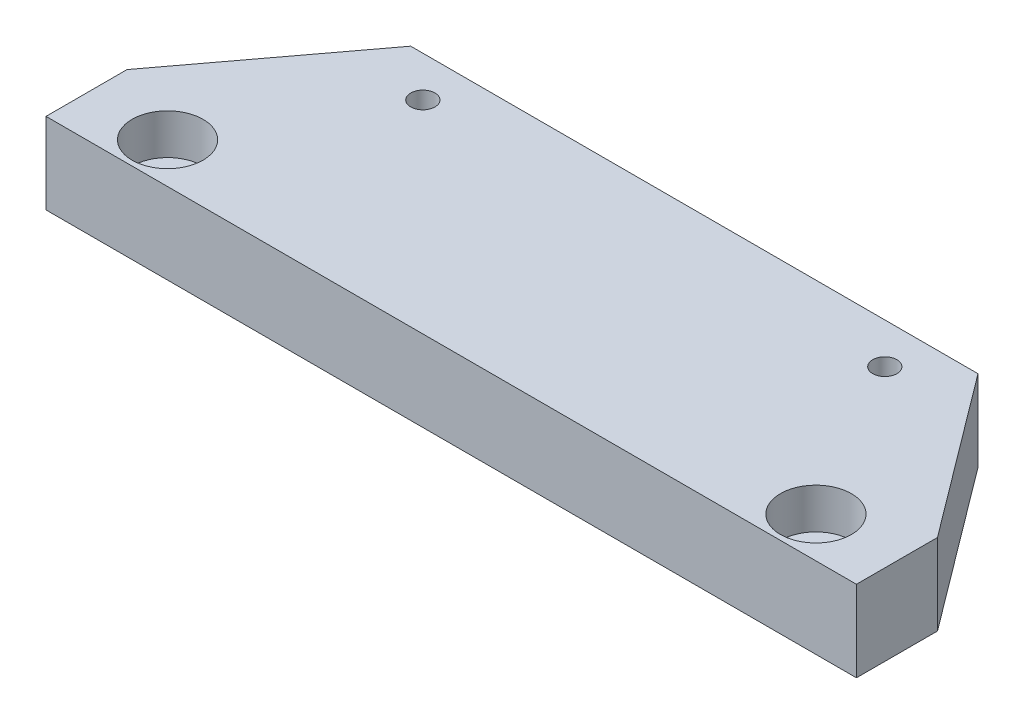
SolidWorks part; units mm, degrees
ref_plane "Front Plane" through (0, 0, 0) normal (0, 0, 1) x (1, 0, 0)
ref_plane "Top Plane" through (0, 0, 0) normal (0, 1, 0) x (1, 0, 0)
ref_plane "Right Plane" through (0, 0, 0) normal (1, 0, 0) x (0, 0, -1)
sketch "Sketch8" plane through (0, 0, 0) normal (0, 1, 0) x (1, 0, 0)
  line L0 (44.45, 0) -> (44.45, -12.7)
  line L1 (0, 0) -> (88.9, 0)
  line L2 (0, 0) -> (0, -12.7)
  line L3 (0, -12.7) -> (88.9, -12.7)
  line L4 (88.9, 0) -> (88.9, -12.7)
  line L5 (8.255, -6.35) -> (80.645, -6.35)
  line L6 (44.45, -12.7) -> (44.45, -31.75)
  line L7 (0, 0) -> (-19.05, -25.4)
  line L8 (-19.05, -25.4) -> (107.95, -25.4)
  line L9 (-19.05, -25.4) -> (-19.05, -38.1)
  line L10 (-19.05, -38.1) -> (107.95, -38.1)
  line L11 (107.95, -25.4) -> (107.95, -38.1)
  line L12 (-19.05, -25.4) -> (107.95, -38.1) construction
  line L13 (-19.05, -38.1) -> (107.95, -25.4) construction
  line L14 (88.9, 0) -> (107.95, -25.4)
  line L15 (95.25, -31.75) -> (-6.35, -31.75)
  point P10 (44.45, -6.35)
  point P23 (44.45, -31.75)
  dimension "D1" = 12.7
  dimension "D2" = 88.9
  dimension "D3" = 72.39
  dimension "D4" = 12.7
  dimension "D5" = 127
  dimension "D6" = 12.7
  dimension "D7" = 101.6
extrude "Boss-Extrude3" add sketch "Sketch8" along normal blind 12.7 contours L7 L8 L6 L3 L2 | L14 L4 L3 L6 L8 | L9 L8 L11 L10 | L2 L1 L4 L3 region at (13.6525, 0, 18.415) region at (75.2475, 0, 18.415)
hole_wizard "CBORE for #6 Socket Head Cap Screw1" positions "Sketch11" profile "Sketch12" counterbore size "#6" standard "ANSI Inch" end condition up to next
sketch "Sketch11" plane through (0, 0, 0) normal (0, -1, 0) x (-1, 0, 0)
  point P0 (-80.645, -6.35)
  point P3 (-8.255, -6.35)
sketch "Sketch12" plane through (80.645, 0, 6.35) normal (1, 0, 0) x (0, 0, -1)
  line L0 (0, 0) -> (0, 12.7)
  line L1 (0, 12.7) -> (1.8986, 12.7)
  line L3 (1.8986, 12.7) -> (1.8986, 3.5052)
  line L4 (1.8986, 3.5052) -> (3.5725, 3.5052)
  line L5 (3.5725, 3.5052) -> (3.5725, 0)
  line L7 (3.5725, 0) -> (0, 0)
  line L11 (0, -6.35) -> (0, 107.95) construction
  dimension "Thru Hole Dia." = 3.7973
  dimension "Thru Hole Depth" = 12.7
  dimension "C'Bore Dia." = 7.145
  dimension "C'Bore Depth" = 3.5052
hole_wizard "CBORE for 1/4 Socket Head Cap Screw1" positions "Sketch13" profile "Sketch14" counterbore size "1/4" standard "ANSI Inch" end condition up to next
sketch "Sketch13" plane through (0, 12.7, 0) normal (0, 1, 0) x (1, 0, 0)
  point P0 (-6.35, -31.75)
  point P3 (95.25, -31.75)
sketch "Sketch14" plane through (-6.35, 12.7, 31.75) normal (1, 0, 0) x (0, 0, 1)
  line L0 (0, 0) -> (0, 12.7)
  line L1 (0, 12.7) -> (3.3782, 12.7)
  line L3 (3.3782, 12.7) -> (3.3782, 6.35)
  line L4 (3.3782, 6.35) -> (5.5562, 6.35)
  line L5 (5.5562, 6.35) -> (5.5562, 0)
  line L7 (5.5562, 0) -> (0, 0)
  line L11 (0, -6.35) -> (0, 107.95) construction
  dimension "Thru Hole Dia." = 6.7564
  dimension "Thru Hole Depth" = 12.7
  dimension "C'Bore Dia." = 11.1125
  dimension "C'Bore Depth" = 6.35
